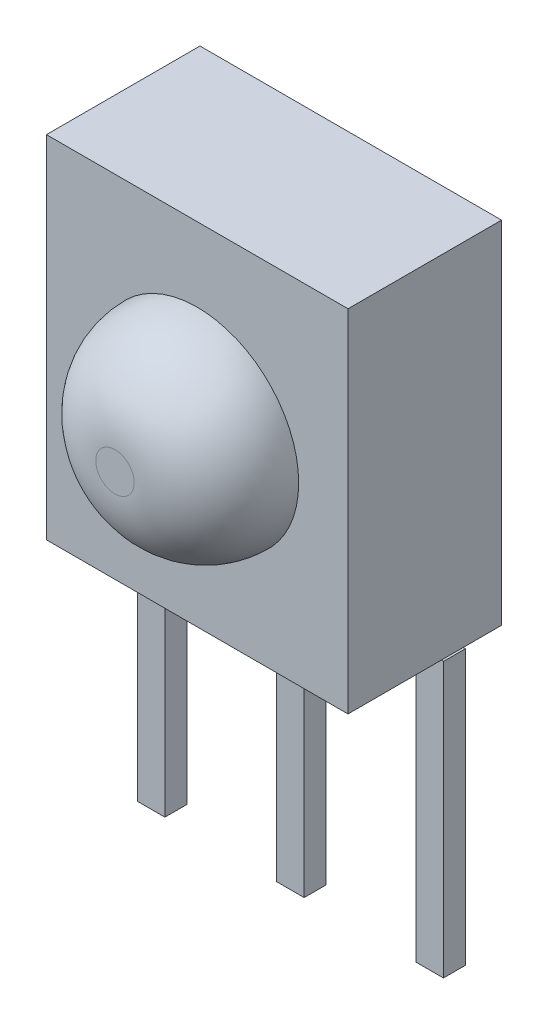
SolidWorks part; units mm, degrees
ref_plane "前视基准面" through (0, 0, 0) normal (0, 0, 1) x (1, 0, 0)
ref_plane "上视基准面" through (0, 0, 0) normal (0, 1, 0) x (1, 0, 0)
ref_plane "右视基准面" through (0, 0, 0) normal (1, 0, 0) x (0, 0, -1)
sketch "草图1" plane through (0, 0, 0) normal (0, 0, 1) x (1, 0, 0)
  line L1 (-2.75, -3.2) -> (2.75, -3.2)
  line L2 (-2.75, -3.2) -> (-2.75, 3.2)
  line L3 (-2.75, 3.2) -> (2.75, 3.2)
  line L4 (2.75, -3.2) -> (2.75, 3.2)
  line L5 (-2.75, -3.2) -> (2.75, 3.2) construction
  line L6 (-2.75, 3.2) -> (2.75, -3.2) construction
  point P0 (0, 0)
  dimension "D1" = 6.4
  dimension "D2" = 5.5
extrude "凸台-拉伸1" add sketch "草图1" along normal blind 2.8
sketch "草图3" plane through (0, 0, 2.8) normal (0, 0, 1) x (1, 0, 0)
  circle A0 centre (0, 0) radius 1.85
  dimension "D1" = 3.7
extrude "凸台-拉伸2" add sketch "草图3" along normal blind 1.5
fillet "圆角1" radius 1.5 1 edges at (1.85, 0, 4.3)
sketch "草图2" plane through (0, -3.2, 0) normal (0, -1, 0) x (1, 0, 0)
  line L0 (-2.75, 0.9) -> (2.75, 0.9) construction
  line L1 (-2.75, 2.8) -> (-2.75, 0) construction
  line L2 (2.75, 2.8) -> (2.75, 0) construction
  line L3 (-2.75, 0) -> (2.75, 0) construction
  line L4 (-0.25, 0.7) -> (-0.25, 1.1)
  line L5 (-2.79, 0.7) -> (-2.29, 0.7)
  line L6 (-2.79, 0.7) -> (-2.79, 1.1)
  line L7 (-2.79, 1.1) -> (-2.29, 1.1)
  line L8 (-2.29, 0.7) -> (-2.29, 1.1)
  line L9 (-2.79, 0.7) -> (-2.29, 1.1) construction
  line L10 (-2.79, 1.1) -> (-2.29, 0.7) construction
  line L11 (-0.25, 0.7) -> (0.25, 0.7)
  line L12 (0.25, 0.7) -> (0.25, 1.1)
  line L13 (-0.25, 1.1) -> (0.25, 1.1)
  line L14 (2.29, 0.7) -> (2.29, 1.1)
  line L15 (2.29, 0.7) -> (2.79, 0.7)
  line L16 (2.79, 0.7) -> (2.79, 1.1)
  line L17 (2.29, 1.1) -> (2.79, 1.1)
  point P8 (0, 0.9)
  point P9 (-2.54, 0.9)
  point P10 (2.54, 0.9)
  point P11 (-2.54, 0.9)
  dimension "D1" = 0.9
  dimension "D2" = 2.54
  dimension "D3" = 2.54
  dimension "D4" = 0.4
  dimension "D5" = 0.5
  dimension "D6" = 3
extrude "凸台-拉伸3" add sketch "草图2" along normal blind 5 separate body
